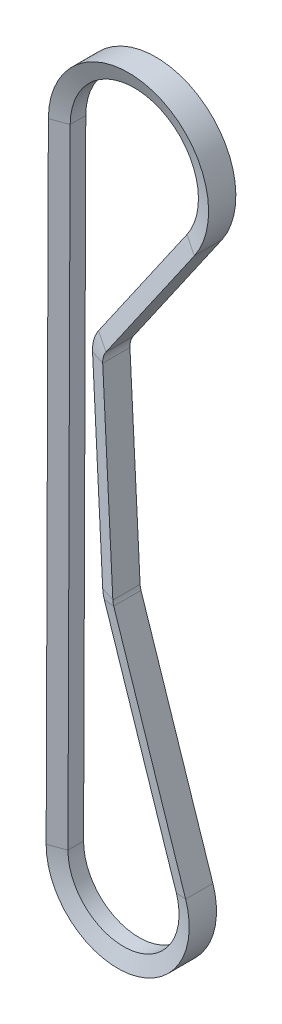
SolidWorks part; units mm, degrees
ref_plane "Front Plane" through (0, 0, 0) normal (0, 0, 1) x (1, 0, 0)
ref_plane "Top Plane" through (0, 0, 0) normal (0, 1, 0) x (1, 0, 0)
ref_plane "Right Plane" through (0, 0, 0) normal (1, 0, 0) x (0, 0, -1)
sketch "Sketch2" plane through (0, 0, 0) normal (0, 0, 1) x (1, 0, 0)
  line L0 (0, 0) -> (1, 0) construction
  line L1 (0, 0) -> (0, 1) construction
  line L12 (-24.9998, 0.0877) -> (-24.2285, 220.0659)
  line L14 (26.7798, 204.0111) -> (-4.1157, 159.4617)
  line L15 (-5.2395, 155.5211) -> (-1.6915, 85.6111)
  line L16 (-1.3797, 83.9427) -> (23.7403, 7.8357)
  arc A4 (-24.2285, 220.0659) -> (26.7798, 204.0111) centre (3.7713, 219.9677) cw
  arc A7 (23.7403, 7.8357) -> (-24.9998, 0.0877) centre (0, 0) cw
  arc A8 (-4.1157, 159.4617) -> (-5.2395, 155.5211) centre (1.1023, 155.843) ccw
  arc A9 (-1.6915, 85.6111) -> (-1.3797, 83.9427) centre (4.6504, 85.933) ccw
ref_plane "Plane4" through (23.7403, 7.8357, 0) normal (0.3134, -0.9496, 0) x (-0.9496, -0.3134, 0)
sketch "Sketch3" plane through (23.7403, 7.8357, 0) normal (0.3134, -0.9496, 0) x (-0.9496, -0.3134, 0)
  line L0 (0, -4.7625) -> (0, 4.7625)
  line L1 (0, -4.7625) -> (5.588, -2.7286)
  line L2 (5.588, -2.7286) -> (5.588, 2.7286)
  line L3 (5.588, 2.7286) -> (0, 4.7625)
  line L4 (0, 0) -> (5.588, 0) construction
  dimension "D1" = 9.525
  dimension "D2" = 5.588
  dimension "D3" = 40
sweep "Sweep1" add profiles "Sketch3" path "Sketch2"
